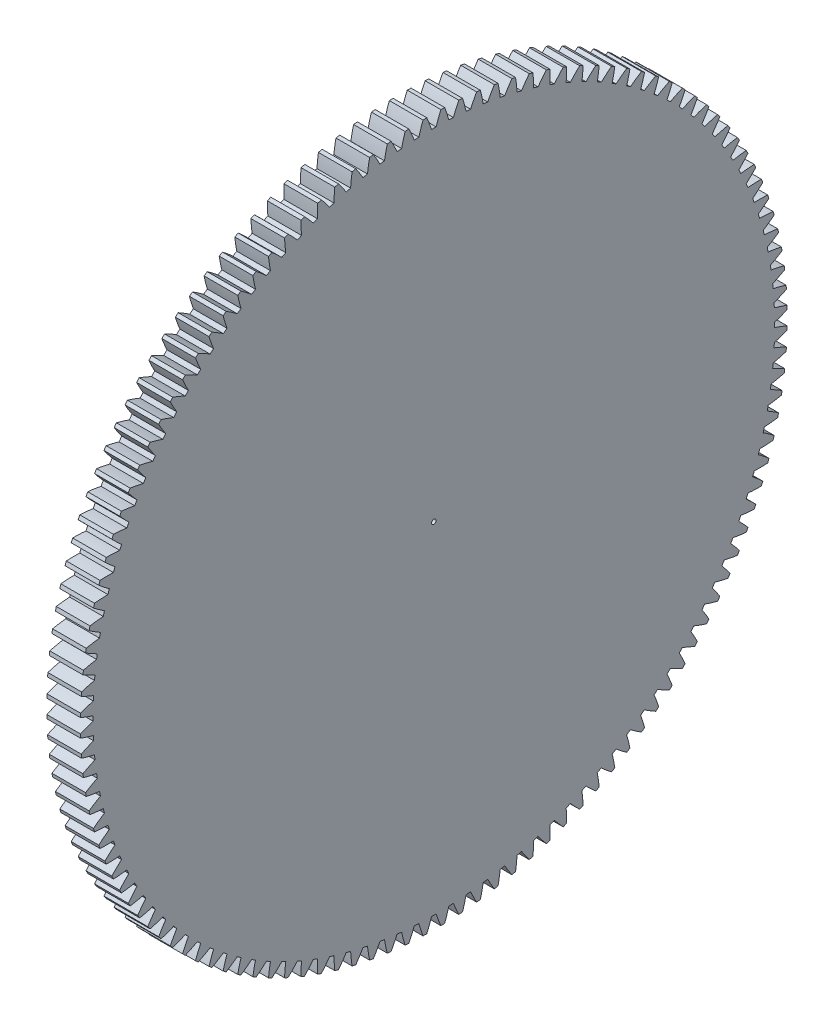
SolidWorks part; units mm, degrees
ref_plane "Plane1" through (0, 0, 0) normal (0, 0, 1) x (1, 0, 0)
ref_plane "Plane2" through (0, 0, 0) normal (0, 1, 0) x (1, 0, 0)
ref_plane "Plane3" through (0, 0, 0) normal (1, 0, 0) x (0, 0, -1)
sketch "HoldingSke" plane through (0, 0, 0) normal (0, 1, 0) x (1, 0, 0)
  line L0 (0, 0) -> (-0.5592, -0.829)
  line L1 (-15, 0) -> (100, 0) construction
  line L2 (0, 0) -> (-2.1039, 2.3779)
  line L3 (0, 0) -> (-11.863, 4.5341)
  line L4 (0, 0) -> (-4.8292, 7.1596)
  line L5 (0, 0) -> (-46.8476, -17.4728)
  line L6 (0, 0) -> (-4.9738, -3.3558)
  line L7 (-2.1039, 2.3779) -> (8.6586, 51.2059)
  line L8 (-76.2, 54.61) -> (-76.1, 54.61)
  line L9 (-71.009, 38.7566) -> (-53.1078, 45.2721)
  line L10 (-76.2, 71.12) -> (104.1128, 71.12)
  line L11 (0, 0) -> (-6, 0)
  line L12 (-76.2, 101.6) -> (-76.162, 101.6)
  line L13 (24.9733, 27.94) -> (52.9518, 28.4284)
  line L14 (24.9733, 27.94) -> (24.9743, 27.94)
  line L15 (24.9733, 27.94) -> (100.4006, 29.5858)
  line L16 (-63.627, -1) -> (-12.827, -1)
  circle A0 centre (0, 0) radius 0.4
  circle A1 centre (0, 0) radius 37.5
  circle A2 centre (0, 0) radius 37.5
  circle A3 centre (0, 0) radius 0.4
  dimension "Num_teeth" = 124
  dimension "Pitch_radius" = 180.3128
  dimension "Width" = 6
  dimension "Thickness" = 6
sketch "BasProSke" plane through (0, 0, 0) normal (0, 1, 0) x (1, 0, 0)
  line L0 (-10, 0) -> (60, 0) construction
  line L1 (0, 0) -> (0, 63)
  line L2 (0, 0) -> (6, 0)
  line L3 (6, 0) -> (6, 63)
  line L4 (6, 63) -> (0, 63)
  dimension "Thickness" = 6
  dimension "Diameter" = 126
revolve "Base-Revolve" add sketch "BasProSke" angle 360 about L0
sketch "TooCutSke" plane through (0, 0, 0) normal (1, 0, 0) x (0, 0, -1)
  line L1 (0, 0) -> (0, 107) construction
  line L2 (0, 0) -> (-0.8519, 61.9941) construction
  line L3 (0, 0) -> (-3.141, 123.9519) construction
  line L4 (-0.8519, 61.9941) -> (-1.5705, 61.9759) construction
  arc A0 (0.4101, 60.7476) -> (-0.4101, 60.7476) centre (0, 0) ccw
  arc A1 (1.2699, 63.0126) -> (-1.2699, 63.0126) centre (0, 0) ccw
  circle A2 centre (0, 0) radius 62 construction
  circle A3 centre (0, 0) radius 58.2609 construction
  arc A4 (-0.4101, 60.7476) -> (-1.2699, 63.0126) centre (-23.9979, 53.089) ccw
  arc A5 (1.2699, 63.0126) -> (0.4101, 60.7476) centre (23.9979, 53.089) ccw
extrude "ToothCut" cut sketch "TooCutSke" along normal through all
fillet "Breaks" [suppressed] radius 0.02 tangent propagation no
fillet "RootFillets" [suppressed] radius 0.251
pattern_circular "TeethCuts" count 124 every 2.903 about axis through (-10, 0, 0) along (1, 0, 0) of "ToothCut", "RootFillets", "Breaks"
sketch "HubNeaOneSke" plane through (0, 0, 0) normal (-1, 0, 0) x (0, 0, 1)
  circle A0 centre (0, 0) radius 37.5
  dimension "Diameter" = 75
extrude "HubNearOne" [suppressed] add sketch "HubNeaOneSke" along normal blind 44.0001
sketch "HubNeaBotSke" plane through (0, 0, 0) normal (-1, 0, 0) x (0, 0, 1)
  circle A0 centre (0, 0) radius 37.5
  dimension "Diameter" = 75
extrude "HubNearBoth" [suppressed] add sketch "HubNeaBotSke" along normal blind 22
ref_plane "FarPln" through (6, 0, 0) normal (1, 0, 0) x (0, 0, -1)
sketch "HubFarSke" plane through (6, 0, 0) normal (1, 0, 0) x (0, 0, -1)
  circle A0 centre (0, 0) radius 37.5
  dimension "Diameter" = 75
extrude "HubFar" [suppressed] add sketch "HubFarSke" along normal blind 22
sketch "BorSke" plane through (0, 0, 0) normal (1, 0, 0) x (0, 0, -1)
  circle A0 centre (0, 0) radius 0.4
  dimension "Diameter" = 0.8
extrude "Bore" cut sketch "BorSke" along normal mid plane 100.0001
sketch "KeySke" plane through (0, 0, 0) normal (1, 0, 0) x (0, 0, -1)
  line L0 (-0.05, 0) -> (-0.05, 0.5)
  line L1 (-0.05, 0.5) -> (0.05, 0.5)
  line L2 (0.05, 0.5) -> (0.05, 0)
  line L3 (0, 0) -> (0, 34) construction
  line L4 (-0.05, 0) -> (0.05, 0)
  dimension "Width" = 0.1
extrude "Keyway" [suppressed] cut sketch "KeySke" along normal mid plane 100.0001
pattern_circular "Keyway2" [suppressed] count 2 every 90 about axis through (-10, 0, 0) along (1, 0, 0) reverse direction yes
equation "' \"Module@HoldingSke\" = 6.35"
equation "' \"Num_teeth@HoldingSke\" = 12"
equation "' \"Ap@HoldingSke\" =  20"
equation "' \"Ap@HoldingSke\" = 20"
equation "' \"Width@HoldingSke\" = 0.5 * 25.4"
equation "' \"Hub_dia@HoldingSke\"= 1 * 25.4"
equation "' \"Hub_dia@HoldingSke\" = 1 * 25.4"
equation "' \"Overall_len@HoldingSke\" = 1.0 * 25.4"
equation "' \"Bore@HoldingSke\" = 0.75 * 25.4"
equation "' \"T_dim@HoldingSke\" = 0.1 * 25.4"
equation "' \"Width@KeySke\" = 0.25 * 25.4"
equation "' \"Show_teeth@HoldingSke\" = 13"
equation "' \"Backlash@HoldingSke\" = 0.009 * 25.4"
equation "' \"Addendum_fac@HoldingSke\" = 1.0"
equation "' \"Dedendum_fac@HoldingSke\" = 1.25"
equation "' \"Dedendum_add@HoldingSke\" = 0.00005 * 25.4"
equation "' \"Clearance_fac@HoldingSke\" = 0.25"
equation "\"Pitch@HoldingSke\" = 1 / \"Module@HoldingSke\""
equation "\"Overcut_dia@TooCutSke\" = (\"Num_teeth@HoldingSke\" + 2 * \"Addendum_fac@HoldingSke\") / \"Pitch@HoldingSke\" + 0.002 * 25.4"
equation "\"Pitch_dia@TooCutSke\" = \"Num_teeth@HoldingSke\" / \"Pitch@HoldingSke\""
equation "\"Base_dia@TooCutSke\" = \"Num_teeth@HoldingSke\" / \"Pitch@HoldingSke\" * cos((\"Ap@HoldingSke\"  * 3.14159265 / 180))"
equation "\"Root_dia@TooCutSke\" = (\"Num_teeth@HoldingSke\" + 2) / \"Pitch@HoldingSke\" - 2 * (\"Addendum_fac@HoldingSke\" + \"Dedendum_fac@HoldingSke\") / \"Pitch@HoldingSke\" - \"Dedendum_add@HoldingSke\" * 2"
equation "\"Half_ang@TooCutSke\" = 180 / \"Num_teeth@HoldingSke\""
equation "\"Half_CT@TooCutSke\" = \"Num_teeth@HoldingSke\" / \"Pitch@HoldingSke\" * sin((3.14159265 / 2 / \"Num_teeth@HoldingSke\")) / 2 - 7 * \"Backlash@HoldingSke\" / 4"
equation "\"Flank_rad@TooCutSke\" = \"Num_teeth@HoldingSke\" / \"Pitch@HoldingSke\" / 5"
equation "\"Radius@RootFillets\" = \"Clearance_fac@HoldingSke\" / \"Pitch@HoldingSke\" + \"Dedendum_add@HoldingSke\""
equation "\"Break_rad@Breaks\" = 0.02 / \"Pitch@HoldingSke\""
equation "\"Thickness@HoldingSke\" = \"Width@HoldingSke\""
equation "\"OAL@HoldingSke\" = \"Thickness@HoldingSke\""
equation "\"MHD@HoldingSke\" = (\"Num_teeth@HoldingSke\" + 2) / \"Pitch@HoldingSke\" - 2 * (\"Addendum_fac@HoldingSke\" + \"Dedendum_fac@HoldingSke\")  / \"Pitch@HoldingSke\" - \"Dedendum_add@HoldingSke\" * 2"
equation "\"MBD@HoldingSke\" = (\"Num_teeth@HoldingSke\" + 2) / \"Pitch@HoldingSke\" - 2 * (\"Addendum_fac@HoldingSke\" + \"Dedendum_fac@HoldingSke\")  / \"Pitch@HoldingSke\" - \"Dedendum_add@HoldingSke\" * 2 - 0.002 * 25.4"
equation "\"MHD@HoldingSke\" = ((sgn( \"MHD@HoldingSke\" - \"Hub_dia@HoldingSke\" )-1)*( \"MHD@HoldingSke\" - \"Hub_dia@HoldingSke\" ))/-2+ \"Hub_dia@HoldingSke\""
equation "\"MBD@HoldingSke\" = ((sgn( \"MBD@HoldingSke\" - \"Bore@HoldingSke\" )-1)*( \"MBD@HoldingSke\" - \"Bore@HoldingSke\" ))/-2+ \"Bore@HoldingSke\""
equation "\"OAL@HoldingSke\" = ((sgn( \"OAL@HoldingSke\" - \"Overall_len@HoldingSke\" )+1)*( \"OAL@HoldingSke\" - \"Overall_len@HoldingSke\" ))/2 + \"Overall_len@HoldingSke\" + 0.000002 * 25.4"
equation "\"Num_teeth@TeethCuts\" = int( \"Show_teeth@HoldingSke\" ) + 1"
equation "\"Num_teeth@TeethCuts\" = ((sgn( \"Num_teeth@TeethCuts\" - \"Num_teeth@HoldingSke\" )-1)*( \"Num_teeth@TeethCuts\" - \"Num_teeth@HoldingSke\" ))/-2+ \"Num_teeth@HoldingSke\""
equation "\"Num_teeth@TeethCuts\" = ((sgn( \"Num_teeth@TeethCuts\" - 2.0)+1)*( \"Num_teeth@TeethCuts\" - 2.0))/2 +2.0"
equation "\"Angle@TeethCuts\" = 360.0 / \"Num_teeth@HoldingSke\""
equation "\"Diameter@BasProSke\" = (\"Num_teeth@HoldingSke\" + 2 * \"Addendum_fac@HoldingSke\") / \"Pitch@HoldingSke\""
equation "\"Thickness@BasProSke\"  = \"Thickness@HoldingSke\""
equation "' \"Fillet_rad@BasProSke\" =  \"Thickness@HoldingSke\" * 0.05"
equation "' \"Fillet_rad@BasProSke\" = \"Thickness@HoldingSke\" * 0.05"
equation "\"MHD@HoldingSke\" = ((sgn( \"MHD@HoldingSke\" - \"Root_dia@TooCutSke\" )-1)*( \"MHD@HoldingSke\" - \"Root_dia@TooCutSke\" ))/-2+ \"Root_dia@TooCutSke\""
equation "\"Diameter@HubNeaOneSke\" = \"MHD@HoldingSke\""
equation "\"Length@HubNearOne\" = \"OAL@HoldingSke\" - \"Thickness@BasProSke\""
equation "\"Diameter@HubNeaBotSke\" = \"MHD@HoldingSke\""
equation "\"Length@HubNearBoth\" = ( \"OAL@HoldingSke\" - \"Thickness@BasProSke\" ) / 2.0"
equation "\"Thickness@FarPln\" = \"Thickness@BasProSke\""
equation "\"Diameter@HubFarSke\" = \"MHD@HoldingSke\""
equation "\"Length@HubFar\" = ( \"OAL@HoldingSke\" - \"Thickness@BasProSke\" ) / 2.0"
equation "\"Diameter@BorSke\" = \"MBD@HoldingSke\""
equation "\"D1@Bore\" = \"OAL@HoldingSke\" * 2.0"
equation "\"D1@Keyway\" = \"OAL@HoldingSke\" * 2.0"
equation "\"Offset@KeySke\" = \"T_dim@HoldingSke\" + \"MBD@HoldingSke\" / 2.0"
